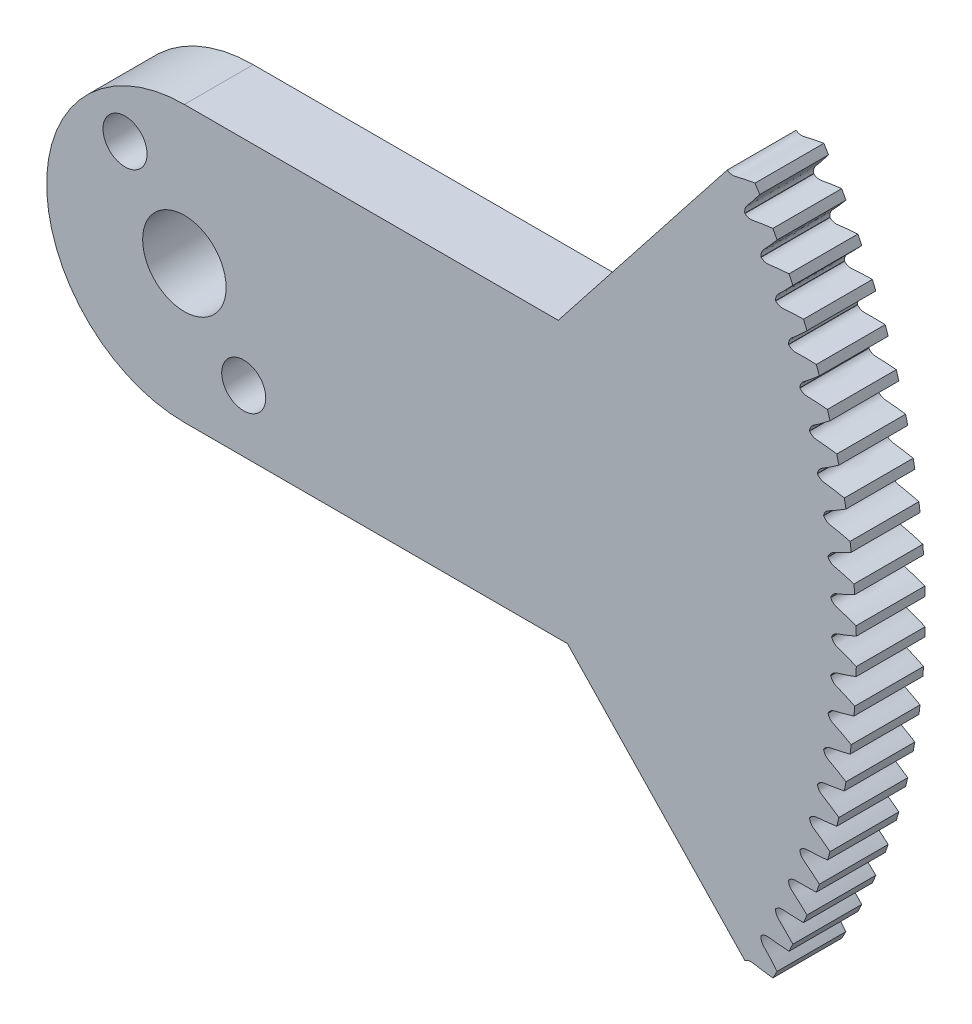
SolidWorks part; units mm, degrees
ref_plane "前视基准面" through (0, 0, 0) normal (0, 0, 1) x (1, 0, 0)
ref_plane "上视基准面" through (0, 0, 0) normal (0, 1, 0) x (1, 0, 0)
ref_plane "右视基准面" through (0, 0, 0) normal (1, 0, 0) x (0, 0, -1)
sketch "草图1" plane through (0, 0, 0) normal (0, 0, 1) x (1, 0, 0)
  circle A0 centre (0, 0) radius 48.8
extrude "凸台-拉伸1" add sketch "草图1" along normal blind 5
ref_axis "基准轴1" through (0, 0, -0.25) along (0, 0, 1)
sketch "草图2" plane through (0, 0, 0) normal (0, 0, 1) x (1, 0, 0)
  line L0 (0, 0) -> (0, 48.8) construction
  circle A0 centre (0, 0) radius 48.8 construction
  arc A1 (0.01, 46.9995) -> (-0.01, 46.9995) centre (0, 0) ccw
  arc A2 (5.357, 55.4832) -> (-5.357, 55.4832) centre (0, 0) ccw
  spline S0 degree 3 poles (0.01, 46.9995) (0.3629, 47.1338) (0.455, 47.5457) (0.6426, 48.0341) (0.7657, 48.3504) (0.9034, 48.6802) (1.0545, 49.0238) (1.2201, 49.3806) (1.4008, 49.7503) (1.597, 50.1324) (1.8094, 50.5263) (2.0385, 50.9317) (2.2848, 51.3478) (2.549, 51.7744) (2.8314, 52.2107) (3.1325, 52.6562) (3.453, 53.1103) (3.7931, 53.5725) (4.1534, 54.0421) (4.6687, 54.6867) (5.0757, 55.1651) (5.357, 55.4832) knots 0 0 0 0 0.090319 0.122121 0.15571 0.191085 0.228245 0.267192 0.307926 0.350445 0.394751 0.440842 0.48872 0.538384 0.589835 0.643071 0.698094 0.754903 0.813498 0.873879 1 1 1 1
  spline S1 degree 3 poles (-0.01, 46.9995) (-0.3629, 47.1338) (-0.455, 47.5457) (-0.6426, 48.0341) (-0.7657, 48.3504) (-0.9034, 48.6802) (-1.0545, 49.0238) (-1.2201, 49.3806) (-1.4008, 49.7503) (-1.597, 50.1324) (-1.8094, 50.5263) (-2.0385, 50.9317) (-2.2848, 51.3478) (-2.549, 51.7744) (-2.8314, 52.2107) (-3.1325, 52.6562) (-3.453, 53.1103) (-3.7931, 53.5725) (-4.1534, 54.0421) (-4.6687, 54.6867) (-5.0757, 55.1651) (-5.357, 55.4832) knots 0 0 0 0 0.090319 0.122121 0.15571 0.191085 0.228245 0.267192 0.307926 0.350445 0.394751 0.440842 0.48872 0.538384 0.589835 0.643071 0.698094 0.754903 0.813498 0.873879 1 1 1 1
extrude "切除-拉伸1" cut sketch "草图2" along normal through all
pattern_circular "阵列(圆周)1" count 120 every 3 about axis through (0, 0, -0.25) along (0, 0, 1) of "切除-拉伸1"
sketch "草图3" plane through (0, 0, 0) normal (0, 0, 1) x (1, 0, 0)
  circle A0 centre (0, 0) radius 48 construction
  dimension "Dn" = 96
sketch "草图4" plane through (0, 0, 5) normal (0, 0, 1) x (1, 0, 0)
  line L0 (0, 0) -> (47.0311, 0) construction
  line L1 (0, 3.5) -> (0, -3.5) construction
  line L2 (-2.5, 2.4495) -> (-2.5, -2.4495)
  line L6 (68.2673, 54.7836) -> (-75.5437, 68.5483)
  line L7 (-75.5437, 68.5483) -> (-61.0104, -72.8558)
  line L8 (-61.0104, -72.8558) -> (125.8378, -56.4021)
  line L10 (0, 6) -> (24, 6)
  line L11 (0, -6) -> (24, -6)
  line L12 (2.5, 2.4495) -> (2.5, -2.4495)
  line L13 (24, 6) -> (39.4225, 25.5894)
  line L14 (-2.5, 3.5) -> (-2.5, -3.5) construction
  line L15 (2.5, 3.5) -> (2.5, -3.5) construction
  line L16 (24, -6) -> (40.7078, -23.4911)
  line L17 (39.4225, 25.5894) -> (68.2673, 54.7836)
  line L18 (24, -6) -> (24, 6)
  line L21 (40.7078, -23.4911) -> (125.8378, -56.4021)
  arc A0 (-2.5, -2.4495) -> (2.5, -2.4495) centre (0, 0) ccw
  arc A2 (0, 6) -> (0, -6) centre (0, 0) ccw
  arc A3 (2.5, 2.4495) -> (-2.5, 2.4495) centre (0, 0) ccw
  point P3 (0, 3)
  point P5 (28.5851, 3)
  point P7 (0, -3)
  point P8 (28.5851, -3)
  dimension "D1" = 7
  dimension "D3" = 12
  dimension "D5" = 24
  dimension "D4" = 2.5
extrude "切除-拉伸3" cut sketch "草图4" against normal up to next contours A2 L10 L6 L7 L8 L11 | A0 region at (0, 0, 5) region at (-6.3785, -5.3011, 5)
sketch "草图5" plane through (0, 0, 5) normal (0, 0, 1) x (1, 0, 0)
  line L4 (-2.55, 2.4698) -> (-2.55, -2.4698)
  line L5 (2.55, -2.4698) -> (2.55, 2.4698)
  line L6 (-2.55, 2.4698) -> (-2.55, -2.4698)
  line L7 (2.55, -2.4698) -> (2.55, 2.4698)
  arc A4 (2.55, 2.4698) -> (-2.55, 2.4698) centre (0, 0) ccw
  arc A5 (-2.55, -2.4698) -> (2.55, -2.4698) centre (0, 0) ccw
  arc A6 (2.55, 2.4698) -> (-2.55, 2.4698) centre (0, 0) ccw
  arc A7 (-2.55, -2.4698) -> (2.55, -2.4698) centre (0, 0) ccw
  dimension "D1" = 0.05
extrude "切除-拉伸4" cut sketch "草图5" against normal blind 10
sketch "草图6" plane through (0, 0, 5) normal (0, 0, 1) x (1, 0, 0)
  circle A0 centre (0, 0) radius 3.55
extrude "切除-拉伸5" cut sketch "草图6" against normal blind 10
sketch "草图7" plane through (0, 0, 0) normal (0, 0, -1) x (-1, 0, 0)
  line L0 (0, 10) -> (-27.1492, 10)
  line L1 (-27.1492, 10) -> (-27.8209, -10)
  line L2 (-27.8209, -10) -> (0, -10)
  arc A0 (0, -10) -> (0, 10) centre (0, 0) ccw
  circle A1 centre (0, 0) radius 3.55 construction
  circle A2 centre (0, 0) radius 3.55
  dimension "D1" = 20
extrude "凸台-拉伸2" add sketch "草图7" against normal up to surface (5 mm away) up to face at (3.55, 0, 5)
sketch "草图8" plane through (0, 0, 0) normal (0, 0, -1) x (-1, 0, 0)
  line L0 (4.3096, 5.5161) -> (0, 0) construction
  line L1 (0, 0) -> (7, 0)
  circle A0 centre (0, 0) radius 7
  circle A1 centre (4.3096, 5.5161) radius 1.6
  circle A2 centre (-4.3096, -5.5161) radius 1.6
  dimension "D1" = 14
  dimension "D3" = 3.2
  dimension "D4" = 3.2
  dimension "D2" = 52
extrude "切除-拉伸6" cut sketch "草图8" against normal blind 10 contours A2 L0 A0 | A0 L0 A2 | L0 A2 A0 | L0 A0 A2 | A1 L0 A0 | A0 L0 A1 | L0 A1 A0 | L0 A0 A1 region at (-4.3862, 4.5541, 0) region at (-4.7068, 6.0244, 0) region at (-3.3577, 5.3576, 0) region at (3.8719, -4.9559, 0) region at (4.7068, -6.0244, 0)
sketch "草图9" plane through (0, 0, 0) normal (0, 0, -1) x (-1, 0, 0)
  circle A0 centre (0, 0) radius 3.55
  circle A1 centre (0, 0) radius 3.03
  dimension "D1" = 6.06
extrude "凸台-拉伸3" add sketch "草图9" against normal up to surface (5 mm away) up to face at (5.9096, -5.5161, 5)
